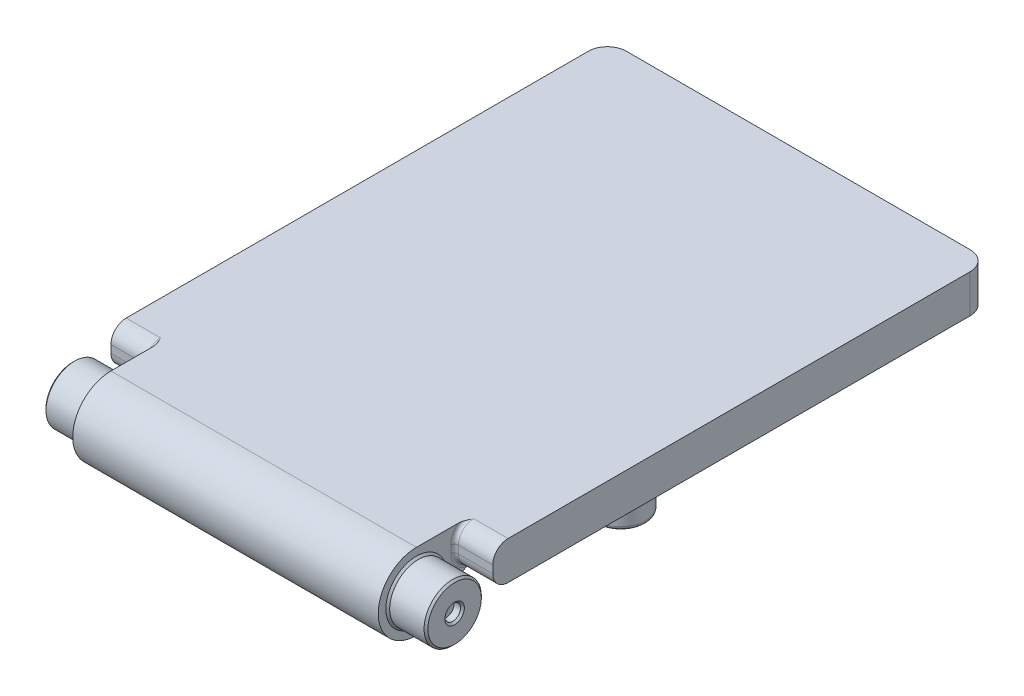
SolidWorks part; units mm, degrees
ref_plane "前视基准面" through (0, 0, 0) normal (0, 0, 1) x (1, 0, 0)
ref_plane "上视基准面" through (0, 0, 0) normal (0, 1, 0) x (1, 0, 0)
ref_plane "右视基准面" through (0, 0, 0) normal (1, 0, 0) x (0, 0, -1)
sketch "草图1" plane through (0, 0, 0) normal (0, 1, 0) x (1, 0, 0)
  line L1 (-50, -75) -> (50, -75)
  line L2 (-50, -75) -> (-50, 75)
  line L3 (-50, 75) -> (50, 75)
  line L4 (50, -75) -> (50, 75)
  line L5 (-50, -75) -> (50, 75) construction
  line L6 (-50, 75) -> (50, -75) construction
  point P0 (0, 0)
  dimension "D1" = 150
  dimension "D2" = 100
extrude "凸台-拉伸1" add sketch "草图1" along normal mid plane 10
sketch "草图3" plane through (50, 0, 0) normal (1, 0, 0) x (0, 0, -1)
  line L1 (-55, -5) -> (-75, -5)
  line L2 (-55, -5) -> (-55, 5)
  line L3 (-55, 5) -> (-75, 5)
  line L4 (-75, -5) -> (-75, 5)
  line L5 (-55, -5) -> (-75, 5) construction
  line L6 (-55, 5) -> (-75, -5) construction
  point P0 (-65, 0)
  point P6 (0, 0)
  dimension "D1" = 20
extrude "切除-拉伸1" cut sketch "草图3" against normal blind 10
extrude "切除-拉伸2" cut sketch "草图3<2>" along normal blind 10 from surface starting at face at (-50, 0, 0)
sketch "草图3<2>" plane through (50, 0, 0) normal (1, 0, 0) x (0, 0, -1) same geometry as "草图3"
sketch "草图4" plane through (40, 0, 0) normal (1, 0, 0) x (0, 0, -1)
  line L0 (-75, 5) -> (-75, -5) construction
  line L1 (-55, -5) -> (-75, -5)
  line L2 (-55, -5) -> (-55, -15)
  line L3 (-55, -15) -> (-75, -15)
  line L4 (-75, -5) -> (-75, -15)
  dimension "D1" = 10
extrude "凸台-拉伸2" add sketch "草图4" against normal blind 80
sketch "草图5" plane through (40, 0, 0) normal (1, 0, 0) x (0, 0, -1)
  line L0 (-55, -5) -> (75, -5) construction
  line L1 (-75, 5) -> (-75, -15) construction
  circle A0 centre (-65, -5) radius 7.5
  point P2 (0, 0)
  dimension "D2" = 15
  dimension "D1" = 10
extrude "凸台-拉伸3" add sketch "草图5" along normal blind 10
sketch "草图6" plane through (50, 0, 0) normal (1, 0, 0) x (0, 0, -1)
  circle A0 centre (-65, -5) radius 2.05
  dimension "D1" = 4.1
extrude "切除-拉伸3" cut sketch "草图6" against normal blind 2.2
chamfer "倒角1" distance 0.5 angle 45 3 edges at (40, -5, 57.5) (50, -5, 57.5) (50, -5, 62.95)
sketch "草图7" plane through (40, 0, 0) normal (1, 0, 0) x (0, 0, -1)
  line L5 (-75, 5) -> (-75, -15)
  line L6 (-75, -15) -> (-55, -15)
  line L7 (-55, -15) -> (-55, -5)
  line L8 (-55, -5) -> (-55, 5)
  line L9 (-55, 5) -> (-75, 5)
  line L10 (-75, 5) -> (-75, -15)
  line L11 (-75, -15) -> (-55, -15)
  line L12 (-55, -15) -> (-55, -5)
  line L13 (-55, -5) -> (-55, 5)
  line L14 (-55, 5) -> (-75, 5)
  circle A0 centre (-65, -5) radius 10
  line M8 (-75, 5) -> (-75, -15)
  line M9 (-75, -15) -> (-55, -15)
  line M10 (-55, -15) -> (-55, -5)
  dimension "D1" = 20
  dimension "D2" = 0
extrude "切除-拉伸4" cut sketch "草图7" against normal through all and the other way through all contours A0 L14 M8 | A0 L10 M9 | A0 L11 M10 region at (40, 2.7663, 72.7663) region at (40, -12.7663, 72.7663) region at (40, -12.7663, 57.2337)
fillet "圆角1" radius 10 1 edges at (0, -5, 55)
mirror "镜向3" about plane through (0, 0, 0) normal (1, 0, 0) of "倒角1", "切除-拉伸3", "凸台-拉伸3"
fillet "圆角2" radius 4 4 edges at (45, 5, 55) (45, -5, 55) (-45, -5, 55) (-45, 5, 55)
fillet "圆角3" radius 1 8 edges at (-40, -5, 49.3397) (-40, -3.8284, 53.8284) (-40, 3.8284, 53.8284) (40, -5, 49.3397) (40, -3.8284, 53.8284) (40, 0, 55) (-40, 0, 55) (40, 3.8284, 53.8284)
sketch "草图9" plane through (0, -5, 0) normal (0, -1, 0) x (1, 0, 0)
  circle A0 centre (13.5, 11.967) radius 6.5 construction
  circle A1 centre (40.5, 11.967) radius 6.5 construction
  circle A2 centre (-13.5, 11.967) radius 6.5 construction
  circle A3 centre (-40.5, 11.967) radius 6.5 construction
  circle A4 centre (13.5, 11.967) radius 6.5
  circle A5 centre (40.5, 11.967) radius 6.5
  circle A6 centre (-13.5, 11.967) radius 6.5
  circle A7 centre (-40.5, 11.967) radius 6.5
extrude "凸台-拉伸4" add sketch "草图9" along normal blind 8
fillet "圆角4" radius 1 8 edges at (40.5, -5, 5.467) (40.5, -13, 5.467) (13.5, -5, 5.467) (13.5, -13, 5.467) (-13.5, -5, 5.467) (-13.5, -13, 5.467) (-40.5, -5, 5.467) (-40.5, -13, 5.467)
fillet "圆角5" radius 5 2 edges at (-50, 0, -75) (50, 0, -75)
